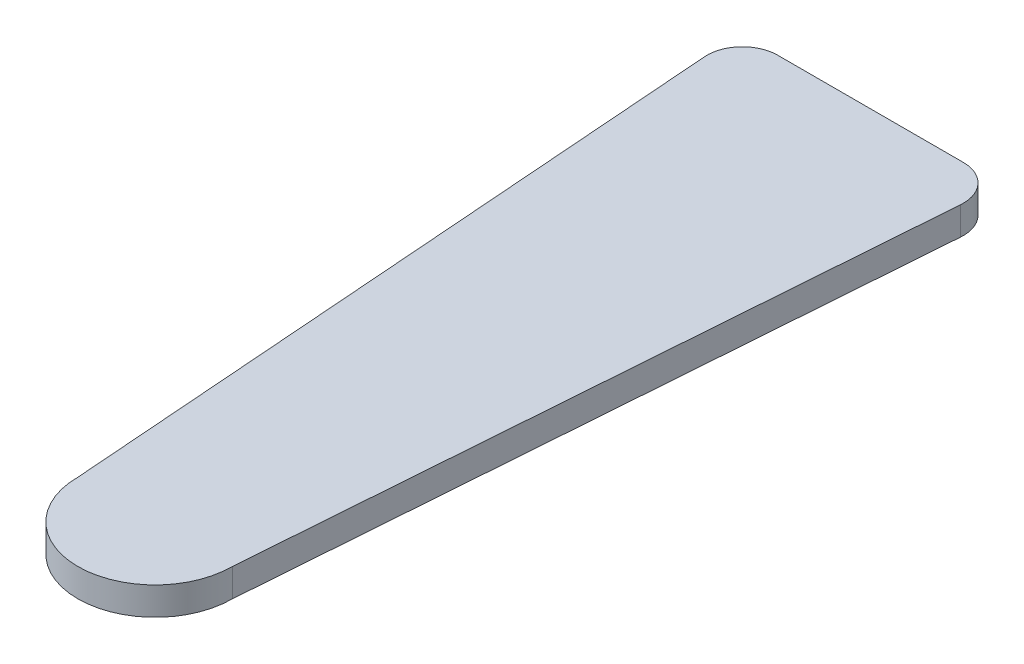
SolidWorks part; units mm, degrees
ref_plane "Front Plane" through (0, 0, 0) normal (0, 0, 1) x (1, 0, 0)
ref_plane "Top Plane" through (0, 0, 0) normal (0, 1, 0) x (1, 0, 0)
ref_plane "Right Plane" through (0, 0, 0) normal (1, 0, 0) x (0, 0, -1)
sketch "Sketch1" plane through (0, 0, 0) normal (0, 1, 0) x (1, 0, 0)
  line L0 (-32.5, 0) -> (-17.5, -200)
  line L2 (17.5, -200) -> (32.5, 0)
  circle A0 centre (0, 0) radius 32.5
  circle A1 centre (0, -200) radius 17.5
  dimension "D1" = 65
  dimension "D2" = 35
  dimension "D3" = 200
extrude "Boss-Extrude1" add sketch "Sketch1" along normal mid plane 6.35 contours L2 A0 L0 | A1 L2 A0 L0 | A1 region at (0, 0, -0.0004) region at (0, 0, 99.8015) region at (0, 0, 200)
sketch "Sketch2" plane through (0, 3.175, 0) normal (0, 1, 0) x (1, 0, 0)
  line L0 (29.65, -38) -> (-29.65, -38)
  line L1 (17.5, -200) -> (32.5, 0) construction
  line L2 (-32.5, 0) -> (-17.5, -200) construction
  line M1 (17.5, -200) -> (32.5, 0)
  arc M2 (32.5, 0) -> (-32.5, 0) centre (0, 0) ccw
  line M3 (-32.5, 0) -> (-17.5, -200)
  dimension "D1" = 38
extrude "Cut-Extrude1" cut sketch "Sketch2" against normal through all contours L0 M1 M2 M3 region at (0, 3.175, 5.2976)
fillet "Fillet2" radius 8 2 edges at (29.65, 0, 38) (-29.65, 0, 38)
